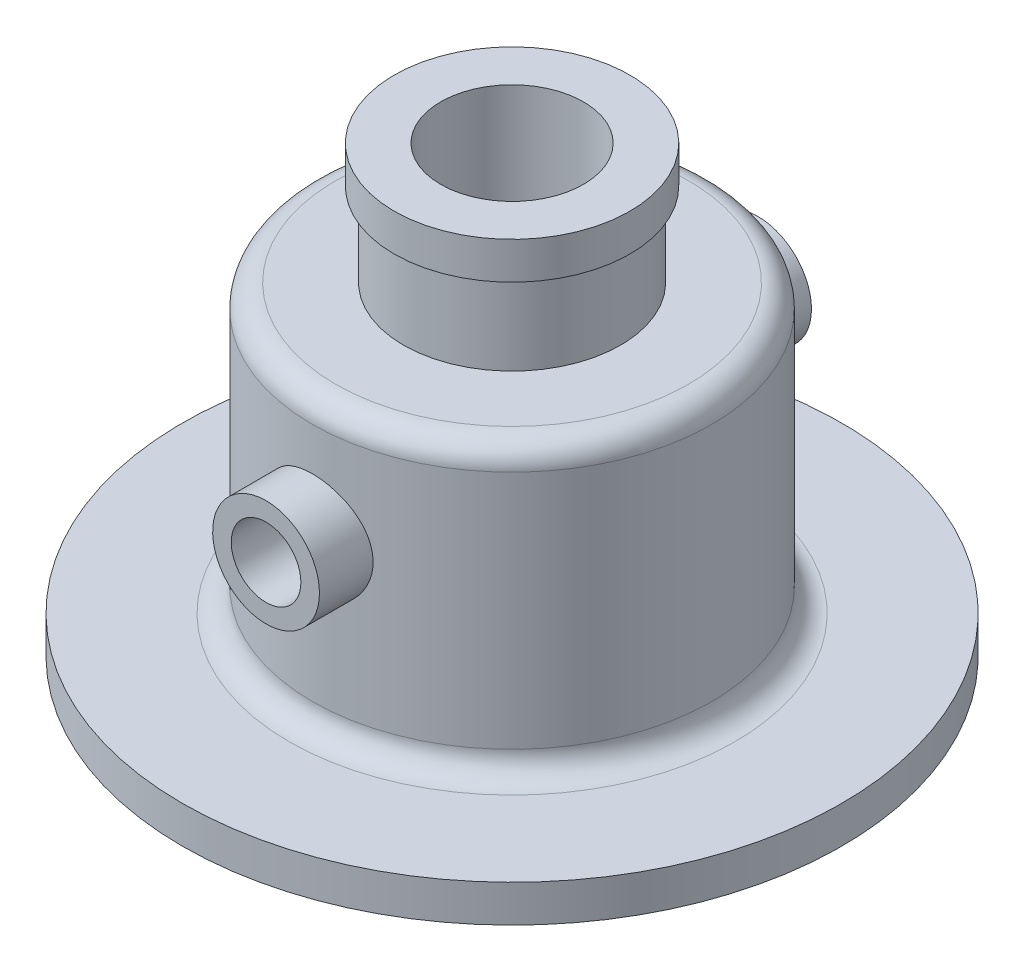
SolidWorks part; units mm, degrees
material "Thornel Mat VMA"
ref_plane "Front Plane" through (0, 0, 0) normal (0, 0, 1) x (1, 0, 0)
ref_plane "Top Plane" through (0, 0, 0) normal (0, 1, 0) x (1, 0, 0)
ref_plane "Right Plane" through (0, 0, 0) normal (1, 0, 0) x (0, 0, -1)
sketch "Sketch2" plane through (0, 0, 0) normal (0, 0, 1) x (1, 0, 0)
  line L0 (0, 50.35) -> (0, -50.35) construction
  line L1 (32, -50.35) -> (32, -47.35)
  line L2 (34, -45.35) -> (71, -45.35)
  line L3 (71, -45.35) -> (71, -37.35)
  line L4 (71, -37.35) -> (48, -37.35)
  line L5 (43, -32.35) -> (43, 19.35)
  line L6 (38, 24.35) -> (23.4, 24.35)
  line L7 (23.4, 24.35) -> (23.4, 42.35)
  line L8 (23.4, 42.35) -> (25.4, 42.35)
  line L9 (25.4, 42.35) -> (25.4, 50.35)
  line L10 (25.4, 50.35) -> (15.4, 50.35)
  line L11 (15.4, 50.35) -> (15.4, 16.1977)
  line L12 (24, -50.35) -> (24, -37.35)
  line L13 (24, -37.35) -> (30, -37.35)
  line L14 (35, -32.35) -> (35, 12.6274)
  line L15 (30, 17.6274) -> (25.4, 17.6274)
  line L16 (25.4, 17.6274) -> (25.4, 13.7743)
  line L17 (25.4, 13.7743) -> (17.4, 13.7743)
  line L18 (24, -50.35) -> (32, -50.35)
  line L19 (15.4, 16.1977) -> (17.4, 13.7743)
  arc A0 (35, 12.6274) -> (30, 17.6274) centre (30, 12.6274) ccw
  arc A1 (30, -37.35) -> (35, -32.35) centre (30, -32.35) ccw
  arc A2 (48, -37.35) -> (43, -32.35) centre (48, -32.35) cw
  arc A3 (43, 19.35) -> (38, 24.35) centre (38, 19.35) ccw
  arc A4 (32, -47.35) -> (34, -45.35) centre (34, -47.35) cw
  point P3 (32, -50.35)
  point P29 (43, -37.35)
  point P32 (43, 24.35)
  point P35 (32, -45.35)
  dimension "D16" = 5
  dimension "D17" = 5
  dimension "D18" = 5
  dimension "D19" = 5
  dimension "D20" = 2
  dimension "D1" = 100.7
  dimension "D2" = 32
  dimension "D3" = 5
  dimension "D4" = 39
  dimension "D5" = 8
  dimension "D6" = 61.7
  dimension "D7" = 19.6
  dimension "D8" = 2
  dimension "D9" = 8
  dimension "D10" = 10
  dimension "D11" = 8
  dimension "D12" = 8
  dimension "D13" = 8
  dimension "D14" = 8
  dimension "D15" = 10
  dimension "D21" = 35
revolve "Revolve1" add sketch "Sketch2" angle 360 about L0
sketch "Sketch3" plane through (0, 0, 0) normal (0, 0, 1) x (1, 0, 0)
  line L0 (25.4, 50.35) -> (-25.4, 50.35) construction
  circle A0 centre (0, -1.35) radius 7.5
  circle A1 centre (0, -1.35) radius 11.5
  dimension "D1" = 15
  dimension "D2" = 51.7
  dimension "D3" = 4
extrude "Boss-Extrude1" add sketch "Sketch3" along normal blind 18 from offset 35 contours A1 | A0
extrude "Boss-Extrude2" add sketch "Sketch3<3>" against normal blind 18 from offset 35 offset against normal yes
sketch "Sketch3<3>" plane through (0, 0, 0) normal (0, 0, 1) x (1, 0, 0) same geometry as "Sketch3"
extrude "Cut-Extrude1" cut sketch "Sketch3<4>" against normal through all both and the other way through all contours A0
sketch "Sketch3<4>" plane through (0, 0, 0) normal (0, 0, 1) x (1, 0, 0) same geometry as "Sketch3"
